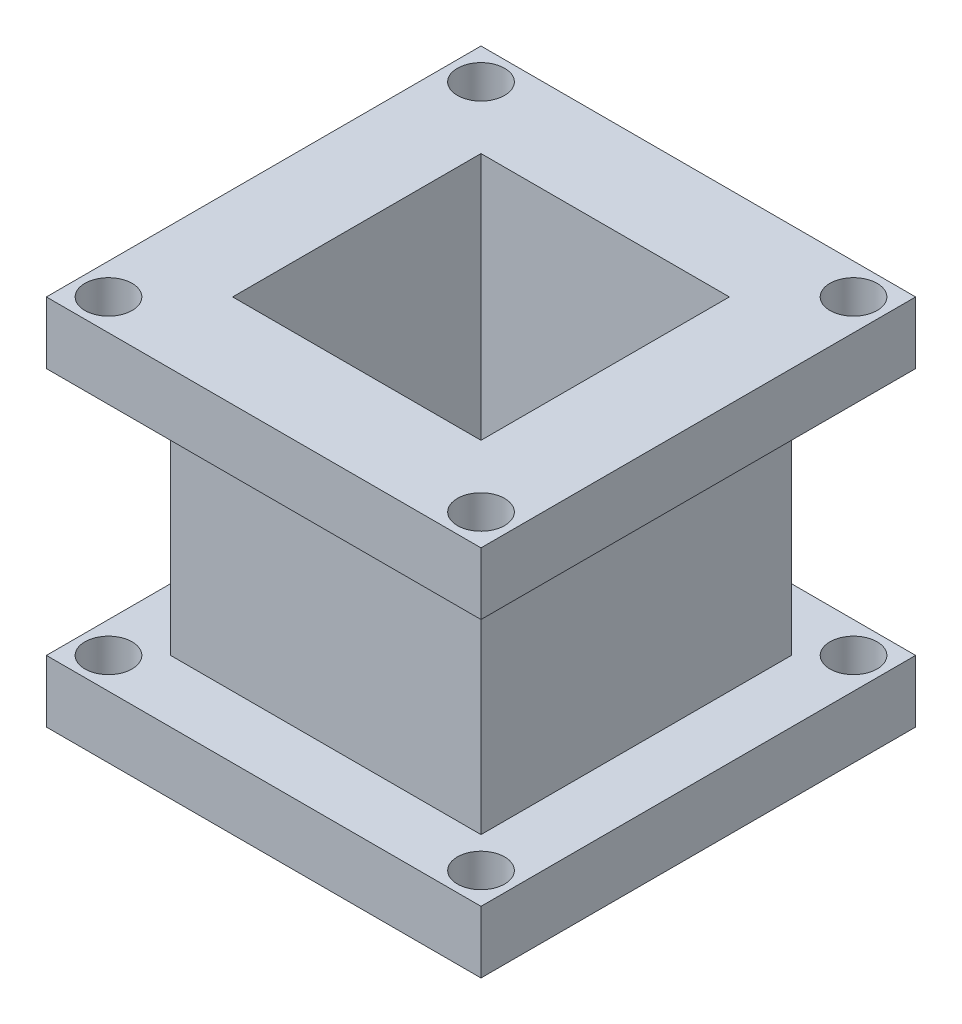
SolidWorks part; units mm, degrees
material "PVAL"
ref_plane "Front Plane" through (0, 0, 0) normal (0, 0, 1) x (1, 0, 0)
ref_plane "Top Plane" through (0, 0, 0) normal (0, 1, 0) x (1, 0, 0)
ref_plane "Right Plane" through (0, 0, 0) normal (1, 0, 0) x (0, 0, -1)
sketch "Sketch1" plane through (0, 0, 0) normal (0, 1, 0) x (1, 0, 0)
  line L1 (-22.225, -22.225) -> (22.225, -22.225)
  line L2 (-22.225, -22.225) -> (-22.225, 22.225)
  line L3 (-22.225, 22.225) -> (22.225, 22.225)
  line L4 (22.225, -22.225) -> (22.225, 22.225)
  line L5 (-22.225, -22.225) -> (22.225, 22.225) construction
  line L6 (-22.225, 22.225) -> (22.225, -22.225) construction
  point P0 (0, 0)
  dimension "D1" = 44.45
  dimension "D2" = 44.45
extrude "Boss-Extrude1" add sketch "Sketch1" along normal blind 6.35
sketch "Sketch2" plane through (0, 6.35, 0) normal (0, 1, 0) x (1, 0, 0)
  line L0 (22.225, 22.225) -> (-22.225, 22.225) construction
  line L1 (-15.875, -15.875) -> (15.875, -15.875)
  line L2 (-15.875, -15.875) -> (-15.875, 15.875)
  line L3 (-15.875, 15.875) -> (15.875, 15.875)
  line L4 (15.875, -15.875) -> (15.875, 15.875)
  line L5 (-15.875, -15.875) -> (15.875, 15.875) construction
  line L6 (-15.875, 15.875) -> (15.875, -15.875) construction
  line L7 (22.225, -22.225) -> (22.225, 22.225) construction
  point P0 (0, 0)
  dimension "D1" = 6.35
  dimension "D2" = 6.35
extrude "Boss-Extrude2" add sketch "Sketch2" along normal blind 25.4 contours L2 L1 L4 L3
sketch "Sketch3" plane through (0, 31.75, 0) normal (0, 1, 0) x (1, 0, 0)
  line L0 (22.225, 22.225) -> (-22.225, 22.225) construction
  line L1 (-22.225, -22.225) -> (22.225, -22.225)
  line L2 (-22.225, -22.225) -> (-22.225, 22.225)
  line L3 (-22.225, 22.225) -> (22.225, 22.225)
  line L4 (22.225, -22.225) -> (22.225, 22.225)
  line L5 (-22.225, -22.225) -> (22.225, 22.225) construction
  line L6 (-22.225, 22.225) -> (22.225, -22.225) construction
  line L7 (22.225, -22.225) -> (22.225, 22.225) construction
  point P0 (0, 0)
  dimension "D1" = 0
  dimension "D2" = 0
extrude "Boss-Extrude3" add sketch "Sketch3" along normal blind 6.35
sketch "Sketch4" plane through (0, 38.1, 0) normal (0, 1, 0) x (1, 0, 0)
  line L1 (-12.7, -12.7) -> (12.7, -12.7)
  line L2 (-12.7, -12.7) -> (-12.7, 12.7)
  line L3 (-12.7, 12.7) -> (12.7, 12.7)
  line L4 (12.7, -12.7) -> (12.7, 12.7)
  line L5 (-12.7, -12.7) -> (12.7, 12.7) construction
  line L6 (-12.7, 12.7) -> (12.7, -12.7) construction
  point P0 (0, 0)
  dimension "D1" = 25.4
  dimension "D2" = 25.4
extrude "Cut-Extrude1" cut sketch "Sketch4" against normal through all
ref_plane "Plane2" through (0, 0, 0) normal (-1, 0, 0) x (0, 0, 1)
ref_axis "Axis2" through (0, 38.1, -36.3412) along (0, 0, 1)
ref_plane "Plane3" through (0, 0, 0) normal (0, 0, 1) x (1, 0, 0)
ref_axis "Axis3" through (-12.7, 38.1, 0) along (1, 0, 0)
ref_plane "Plane4" through (0, 38.1, 0) normal (0, 1, 0) x (1, 0, 0)
ref_axis "Axis4" through (0, -1.905, 0) along (0, 1, 0)
sketch "Sketch6" plane through (0, 31.75, 0) normal (0, -1, 0) x (1, 0, 0)
  line L0 (22.225, 22.225) -> (15.875, 15.875) construction
  circle A1 centre (19.05, 19.05) radius 2.413
  dimension "D1" = 4.826
extrude "Cut-Extrude3" cut sketch "Sketch6" against normal through all and the other way through all
pattern_circular "CirPattern1" count 4 over 360 about axis through (0, -1.905, 0) along (0, 1, 0) of "Cut-Extrude3"
